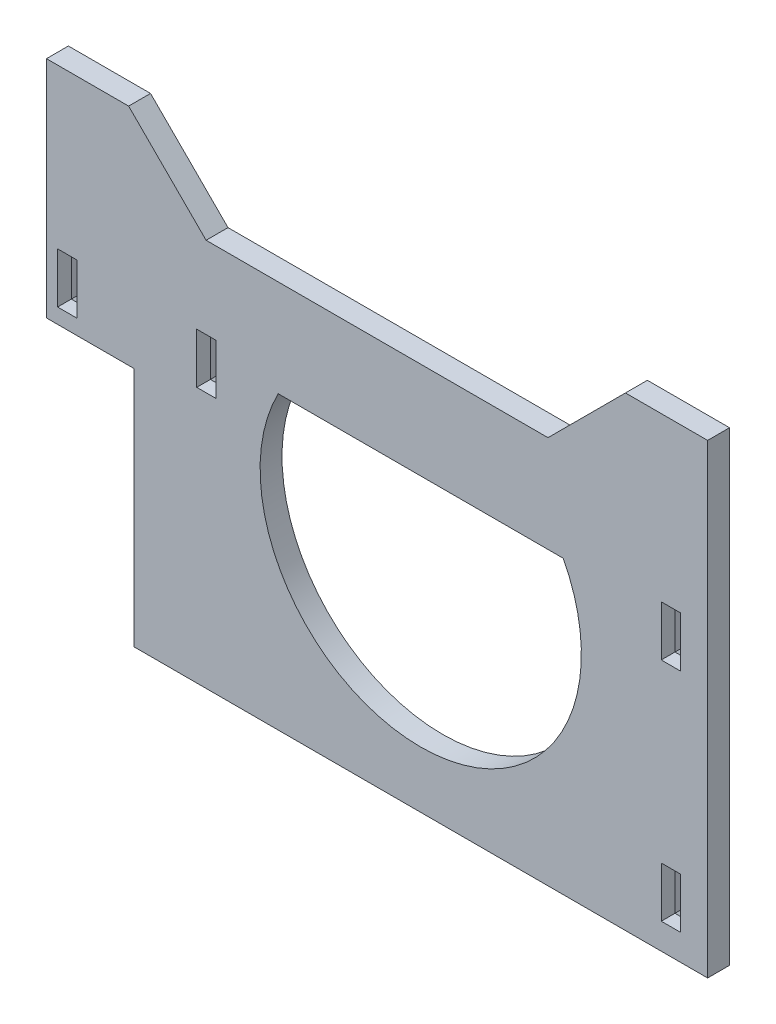
SolidWorks part; units mm, degrees
ref_plane "Front Plane" through (0, 0, 0) normal (0, 0, 1) x (1, 0, 0)
ref_plane "Top Plane" through (0, 0, 0) normal (0, 1, 0) x (1, 0, 0)
ref_plane "Right Plane" through (0, 0, 0) normal (1, 0, 0) x (0, 0, -1)
sketch "Sketch1" plane through (0, 0, 0) normal (0, 0, 1) x (1, 0, 0)
  line L0 (-25.9, 23.1791) -> (26.1356, 23.1791)
  line L6 (-40.7725, 25.95) -> (-37.2425, 25.95)
  line L9 (-40.7725, 25.95) -> (-40.7725, 16.75)
  line L12 (-40.7725, 16.75) -> (-37.2425, 16.75)
  line L15 (-37.2425, 25.95) -> (-37.2425, 16.75)
  line L51 (52.4925, 30) -> (52.4925, -30)
  line L54 (44.0275, 25.25) -> (47.5575, 25.25)
  line L55 (44.0275, 25.25) -> (44.0275, 16.05)
  line L56 (44.0275, 16.05) -> (47.5575, 16.05)
  line L57 (47.5575, 25.25) -> (47.5575, 16.05)
  line L58 (47.565, -16.05) -> (44.035, -16.05)
  line L59 (47.565, -16.05) -> (47.565, -25.25)
  line L60 (47.565, -25.25) -> (44.035, -25.25)
  line L61 (44.035, -16.05) -> (44.035, -25.25)
  line L65 (-66.1725, 25.95) -> (-62.6425, 25.95)
  line L66 (-66.1725, 25.95) -> (-66.1725, 16.75)
  line L67 (-66.1725, 16.75) -> (-62.6425, 16.75)
  line L68 (-62.6425, 25.95) -> (-62.6425, 16.75)
  line L76 (52.4925, 30) -> (-68.2075, 30)
  line L81 (-39.0075, 25.95) -> (-39.0075, 16.75) construction
  line L82 (-37.2425, 21.35) -> (-40.7725, 21.35) construction
  line L83 (-64.4075, 25.95) -> (-64.4075, 16.75) construction
  line L84 (-62.6425, 21.35) -> (-66.1725, 21.35) construction
  line L85 (47.5575, 20.65) -> (44.0275, 20.65) construction
  line L86 (45.7925, 25.25) -> (45.7925, 16.05) construction
  line L87 (45.8, -16.05) -> (45.8, -25.25) construction
  line L88 (47.565, -20.65) -> (44.035, -20.65) construction
  line L89 (-52.2075, -30) -> (-52.2075, 14)
  line L90 (-52.2075, 14) -> (-68.2075, 14)
  line L91 (-68.2075, 14) -> (-68.2075, 30)
  line L92 (-52.2075, -30) -> (52.4925, -30)
  arc A12 (-25.9, 23.1791) -> (26.1356, 23.1791) centre (0.1178, 9.6488) ccw
  point P0 (-0.0075, 0)
  point P14 (52.4925, 0)
  point P25 (-7.8575, 30)
  dimension "D3" = 3.53
  dimension "D4" = 9.2
  dimension "D6" = 60
  dimension "D5" = 25.4
  dimension "D7" = 53.65
  dimension "D2" = 31.15
  dimension "D10" = 20.65
  dimension "D11" = 20.65
  dimension "D8" = 120.7
  dimension "D9" = 16
  dimension "D12" = 44
extrude "Boss-Extrude1" add sketch "Sketch1" along normal blind 4
sketch "Sketch2" plane through (0, 0, 0) normal (0, 0, 1) x (1, 0, 0)
  line L0 (-68.2075, 30) -> (52.4925, 30)
  line L4 (23.3504, 40.8579) -> (-39.0654, 40.8579)
  line L5 (-39.0654, 40.8579) -> (-53.2075, 55)
  line L6 (-53.2075, 55) -> (-68.2075, 55)
  line L7 (-68.2075, 55) -> (-68.2075, 30)
  line L8 (23.3504, 40.8579) -> (37.4925, 55)
  line L9 (37.4925, 55) -> (52.4925, 55)
  line L10 (52.4925, 55) -> (52.4925, 30)
  line L12 (-68.2075, 30) -> (-68.2075, 14) construction
  dimension "D1" = 25
  dimension "D2" = 20
  dimension "D3" = 15
  dimension "D4" = 135
extrude "Boss-Extrude2" add sketch "Sketch2" along normal blind 4
sketch "Sketch3" plane through (0, 0, 0) normal (0, 0, -1) x (-1, 0, 0)
  line L0 (-45.7925, 25.25) -> (-45.7925, 16.05) construction
  line L1 (-47.5575, 25.25) -> (-44.0275, 25.25) construction
  line L2 (-44.0275, 16.05) -> (-47.5575, 16.05) construction
  line L3 (-47.5575, 20.65) -> (-44.0275, 20.65) construction
  line L4 (-47.5575, 16.05) -> (-47.5575, 25.25) construction
  line L5 (-44.0275, 25.25) -> (-44.0275, 16.05) construction
  line L6 (-45.8, -16.05) -> (-45.8, -25.25) construction
  line L7 (-47.565, -16.05) -> (-44.035, -16.05) construction
  line L8 (-44.035, -25.25) -> (-47.565, -25.25) construction
  line L9 (-47.565, -20.65) -> (-44.035, -20.65) construction
  line L10 (-47.565, -25.25) -> (-47.565, -16.05) construction
  line L11 (-44.035, -16.05) -> (-44.035, -25.25) construction
  line L12 (39.0075, 25.95) -> (39.0075, 16.75) construction
  line L13 (37.2425, 25.95) -> (40.7725, 25.95) construction
  line L14 (40.7725, 16.75) -> (37.2425, 16.75) construction
  line L15 (37.2425, 21.35) -> (40.7725, 21.35) construction
  line L16 (37.2425, 16.75) -> (37.2425, 25.95) construction
  line L17 (40.7725, 25.95) -> (40.7725, 16.75) construction
  line L18 (64.4075, 25.95) -> (64.4075, 16.75) construction
  line L19 (62.6425, 25.95) -> (66.1725, 25.95) construction
  line L20 (66.1725, 16.75) -> (62.6425, 16.75) construction
  line L21 (62.6425, 21.35) -> (66.1725, 21.35) construction
  line L22 (62.6425, 16.75) -> (62.6425, 25.95) construction
  line L23 (66.1725, 25.95) -> (66.1725, 16.75) construction
chamfer "Chamfer1" distance 1.5 distance2 0.5 16 edges at (45.8, -25.25, 0) (44.035, -20.65, 0) (45.8, -16.05, 0) (47.565, -20.65, 0) (-64.4075, 25.95, 0) (-62.6425, 21.35, 0) (-64.4075, 16.75, 0) (-66.1725, 21.35, 0) (-39.0075, 25.95, 0) (-37.2425, 21.35, 0) (-39.0075, 16.75, 0) (-40.7725, 21.35, 0) (45.7925, 25.25, 0) (47.5575, 20.65, 0) (45.7925, 16.05, 0) (44.0275, 20.65, 0) first distance on face at (45.8, -25.25, 2) first distance on face at (44.035, -20.65, 2) first distance on face at (45.8, -16.05, 2) first distance on face at (47.565, -20.65, 2) first distance on face at (-64.4075, 25.95, 2) first distance on face at (-62.6425, 21.35, 2) first distance on face at (-64.4075, 16.75, 2) first distance on face at (-66.1725, 21.35, 2) first distance on face at (-39.0075, 25.95, 2) first distance on face at (-37.2425, 21.35, 2) first distance on face at (-39.0075, 16.75, 2) first distance on face at (-40.7725, 21.35, 2) first distance on face at (45.7925, 25.25, 2) first distance on face at (47.5575, 20.65, 2) first distance on face at (45.7925, 16.05, 2) first distance on face at (44.0275, 20.65, 2)
equation "\"pin_hole_width\"=3.53"
equation "\"D3@Sketch1\"=\"pin_hole_width\""
equation "\"pin_hole_height\"=9.2"
equation "\"D4@Sketch1\"=\"pin_hole_height\""
